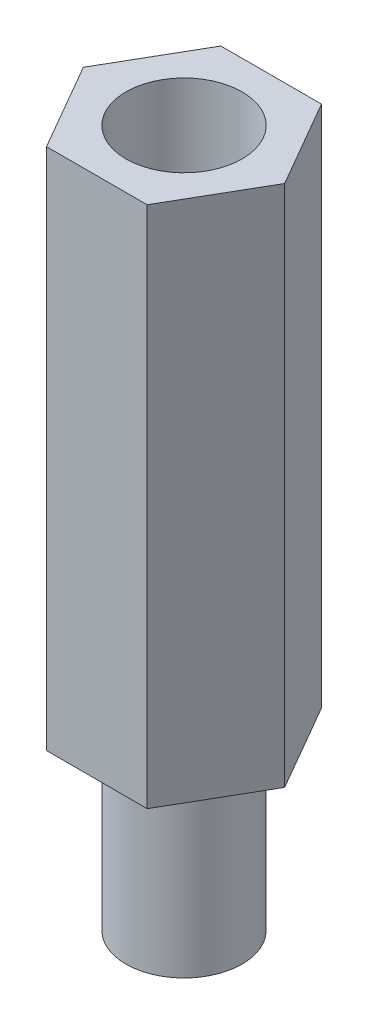
SolidWorks part; units mm, degrees
material "铜"
ref_plane "前视基准面" through (0, 0, 0) normal (0, 0, 1) x (1, 0, 0)
ref_plane "上视基准面" through (0, 0, 0) normal (0, 1, 0) x (1, 0, 0)
ref_plane "右视基准面" through (0, 0, 0) normal (1, 0, 0) x (0, 0, -1)
sketch "草图2" plane through (0, 0, 0) normal (0, 1, 0) x (1, 0, 0)
  line L1 (3.4641, 0) -> (1.7321, 3)
  line L2 (1.7321, 3) -> (-1.7321, 3)
  line L3 (-1.7321, 3) -> (-3.4641, 0)
  line L4 (-3.4641, 0) -> (-1.7321, -3)
  line L5 (-1.7321, -3) -> (1.7321, -3)
  line L6 (1.7321, -3) -> (3.4641, 0)
  circle A0 centre (0, 0) radius 3 construction
  circle A1 centre (0, 0) radius 2
  dimension "D2" = 4
  dimension "D1" = 6
extrude "凸台-拉伸1" add sketch "草图2" along normal blind 18
extrude "凸台-拉伸2" add sketch "草图2<2>" against normal blind 6 separate body contours A1 region at (0, 0, 0)
sketch "草图2<2>" plane through (0, 0, 0) normal (0, 1, 0) x (1, 0, 0) same geometry as "草图2"
